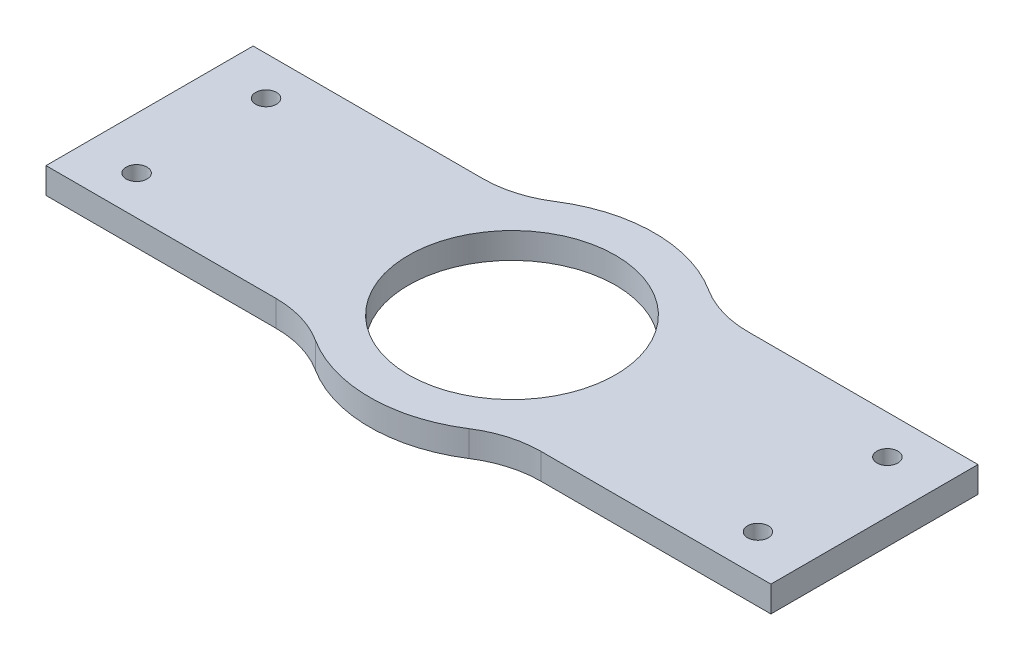
SolidWorks part; units mm, degrees
material "6061-T6 (SS)"
ref_plane "Front" through (0, 0, 0) normal (0, 0, 1) x (1, 0, 0)
ref_plane "Top" through (0, 0, 0) normal (0, 1, 0) x (1, 0, 0)
ref_plane "Right" through (0, 0, 0) normal (1, 0, 0) x (0, 0, -1)
sketch "Sketch1" plane through (0, 0, 0) normal (0, 1, 0) x (1, 0, 0)
  line L0 (177.8, 0) -> (177.8, 19.05) construction
  line L1 (0, 0) -> (56.3659, 0)
  line L2 (0, 0) -> (0, 50.8)
  line L3 (0, 50.8) -> (56.3659, 50.8)
  line L4 (177.8, 0) -> (177.8, 50.8)
  line L5 (0, 50.8) -> (177.8, 0) construction
  line L6 (121.4341, 50.8) -> (177.8, 50.8)
  line L7 (121.4341, 0) -> (177.8, 0)
  arc A0 (70.0645, -4.0105) -> (107.7355, -4.0105) centre (88.9, 25.4) ccw
  arc A1 (107.7355, 54.8105) -> (70.0645, 54.8105) centre (88.9, 25.4) ccw
  arc A2 (56.3659, 0) -> (70.0645, -4.0105) centre (56.3659, -25.4) cw
  arc A3 (121.4341, 0) -> (107.7355, -4.0105) centre (121.4341, -25.4) ccw
  arc A4 (121.4341, 50.8) -> (107.7355, 54.8105) centre (121.4341, 76.2) cw
  arc A5 (56.3659, 50.8) -> (70.0645, 54.8105) centre (56.3659, 76.2) ccw
  point P18 (112.8707, 50.8)
  dimension "D2" = 69.85
  dimension "D3" = 25.4
  dimension "D1" = 50.8
extrude "Boss-Extrude1" add sketch "Sketch1" along normal blind 6.35
sketch "Sketch4" plane through (0, 6.35, 0) normal (0, 1, 0) x (1, 0, 0)
  line L0 (0, 0) -> (12.7, 9.525) construction
  line L1 (0, 0) -> (56.3659, 0) construction
  line L6 (12.7, 9.525) -> (12.7, 41.275) construction
  line L7 (12.7, 41.275) -> (25.4, 50.8) construction
  line L8 (56.3659, 50.8) -> (0, 50.8) construction
  line L9 (88.9, 0) -> (88.9, 25.4) construction
  arc A0 (70.0645, -4.0105) -> (107.7355, -4.0105) centre (88.9, 25.4) ccw construction
  point P0 (12.7, 41.275)
  point P4 (12.7, 9.525)
  point P34 (165.1, 9.525)
  point P36 (165.1, 41.275)
  dimension "D1" = 31.75
  dimension "D2" = 25.4
hole_wizard "#10 Clearance Hole1" positions "Sketch4" profile "Sketch3" hole size "#10" standard "ANSI Inch" end condition up to next
sketch "Sketch3" plane through (12.7, 6.35, -41.275) normal (1, 0, 0) x (0, 0, 1)
  line L0 (0, 0) -> (0, 6.35)
  line L1 (0, 6.35) -> (2.5527, 6.35)
  line L2 (2.5527, 6.35) -> (2.5527, 0)
  line L5 (2.5527, 0) -> (0, 0)
  line L11 (0, -6.35) -> (0, 107.95) construction
  dimension "Thru Hole Dia." = 5.1054
  dimension "Thru Hole Depth" = 6.35
sketch "Sketch5" plane through (0, 6.35, 0) normal (0, 1, 0) x (1, 0, 0)
  circle A0 centre (88.9, 25.4) radius 25.4
  arc A1 (107.7355, 54.8105) -> (70.0645, 54.8105) centre (88.9, 25.4) ccw construction
  dimension "D1" = 50.8
extrude "Cut-Extrude1" cut sketch "Sketch5" against normal through all
